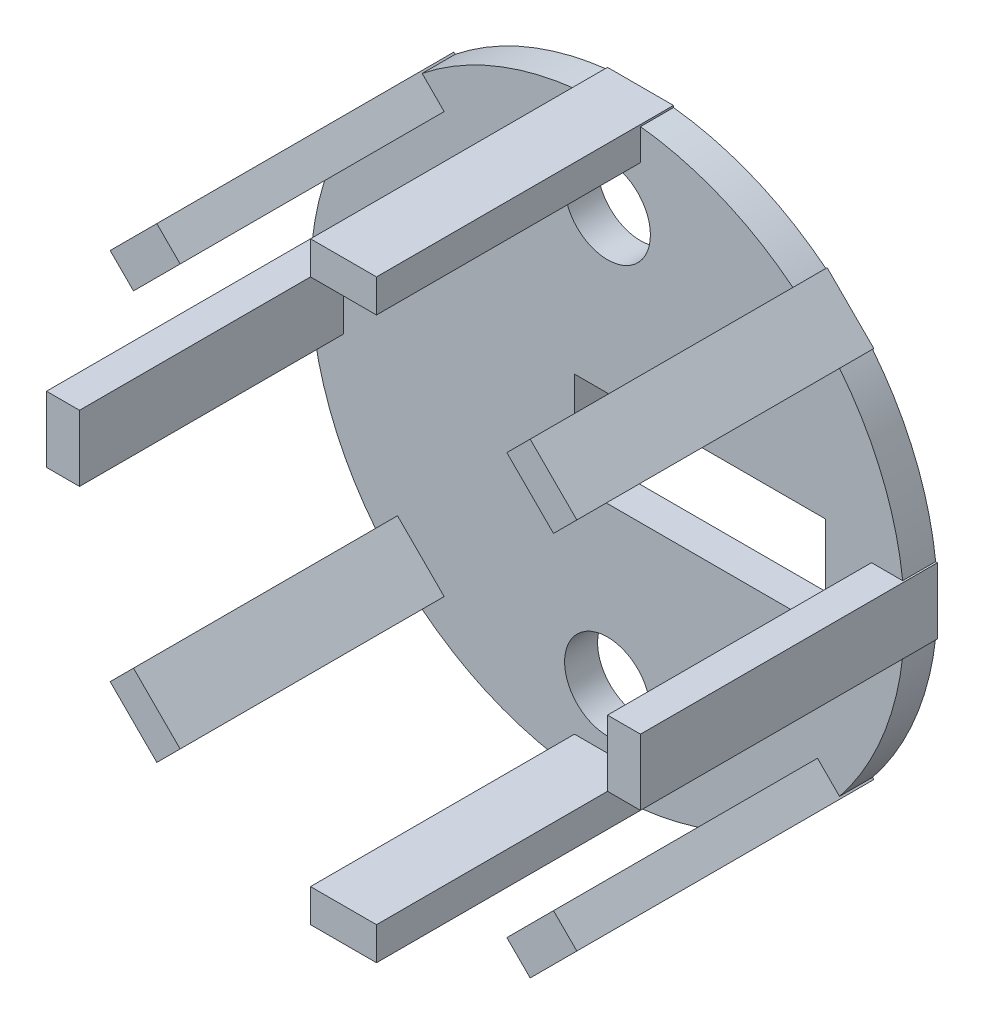
SolidWorks part; units mm, degrees
ref_plane "正面" through (0, 0, 0) normal (0, 0, 1) x (1, 0, 0)
ref_plane "平面" through (0, 0, 0) normal (0, 1, 0) x (1, 0, 0)
ref_plane "右側面" through (0, 0, 0) normal (1, 0, 0) x (0, 0, -1)
sketch "ｽｹｯﾁ1" plane through (0, 0, 0) normal (0, 0, 1) x (1, 0, 0)
  circle A0 centre (0, 0) radius 9
  dimension "D1" = 18
extrude "ﾎﾞｽ - 押し出し1" add sketch "ｽｹｯﾁ1" along normal blind 1
sketch "ｽｹｯﾁ3" plane through (0, 0, 0) normal (0, 0, 1) x (1, 0, 0)
  circle A0 centre (0, 0) radius 10.05
  dimension "D1" = 20.1
extrude "ｶｯﾄ - 押し出し3" [suppressed] cut sketch "ｽｹｯﾁ3" along normal blind 4.5
sketch "ｽｹｯﾁ2" plane through (0, 0, 0) normal (0, 0, 1) x (1, 0, 0)
  circle A0 centre (0, 6.25) radius 1.3
  circle A1 centre (0, -6.25) radius 1.3
  dimension "D1" = 2.6
  dimension "D2" = 2.6
  dimension "D3" = 6.25
  dimension "D4" = 6.25
extrude "ｶｯﾄ - 押し出し1" cut sketch "ｽｹｯﾁ2" along normal through all
sketch "ｽｹｯﾁ4" plane through (0, 0, 0) normal (0, 0, 1) x (1, 0, 0)
  line L5 (6.6, -1.45) -> (0, 0) construction
  line L6 (6.6, 1.45) -> (0, 0) construction
  line L7 (6.6, -1.45) -> (-1, -1.45)
  line L8 (6.6, -1.45) -> (6.6, 1.45)
  line L9 (6.6, 1.45) -> (-1, 1.45)
  line L10 (-1, -1.45) -> (-1, 1.45)
  point P0 (0, 0)
  point P1 (-1, 0)
  dimension "D1" = 2.9
  dimension "D2" = 7.6
  dimension "D3" = 1
extrude "ｶｯﾄ - 押し出し6" cut sketch "ｽｹｯﾁ4" along normal through all
sketch "ｽｹｯﾁ5" plane through (0, 0, 0) normal (0, 0, 1) x (1, 0, 0)
  line L0 (-6.364, 4.9497) -> (-4.9497, 6.364)
  line L1 (-8, -1) -> (-9, -1)
  line L2 (-8, -1) -> (-8, 1)
  line L3 (-8, 1) -> (-9, 1)
  line L4 (-9, -1) -> (-9, 1)
  line L5 (-8, -1) -> (-9, 1) construction
  line L6 (-8, 1) -> (-9, -1) construction
  line L7 (-7.0711, 5.6569) -> (-5.6569, 7.0711)
  line L8 (-4.9497, 6.364) -> (-5.6569, 7.0711)
  line L9 (-6.364, 4.9497) -> (-7.0711, 5.6569)
  line L10 (-1, 8) -> (1, 8)
  line L11 (-1, 9) -> (1, 9)
  line L12 (1, 8) -> (1, 9)
  line L13 (-1, 8) -> (-1, 9)
  line L14 (4.9497, 6.364) -> (6.364, 4.9497)
  line L15 (5.6569, 7.0711) -> (7.0711, 5.6569)
  line L16 (6.364, 4.9497) -> (7.0711, 5.6569)
  line L17 (4.9497, 6.364) -> (5.6569, 7.0711)
  line L18 (8, 1) -> (8, -1)
  line L19 (9, 1) -> (9, -1)
  line L20 (8, -1) -> (9, -1)
  line L21 (8, 1) -> (9, 1)
  line L22 (6.364, -4.9497) -> (4.9497, -6.364)
  line L23 (7.0711, -5.6569) -> (5.6569, -7.0711)
  line L24 (4.9497, -6.364) -> (5.6569, -7.0711)
  line L25 (6.364, -4.9497) -> (7.0711, -5.6569)
  line L26 (1, -8) -> (-1, -8)
  line L27 (1, -9) -> (-1, -9)
  line L28 (-1, -8) -> (-1, -9)
  line L29 (1, -8) -> (1, -9)
  line L30 (-4.9497, -6.364) -> (-6.364, -4.9497)
  line L31 (-5.6569, -7.0711) -> (-7.0711, -5.6569)
  line L32 (-6.364, -4.9497) -> (-7.0711, -5.6569)
  line L33 (-4.9497, -6.364) -> (-5.6569, -7.0711)
  circle A0 centre (0, 0) radius 9 construction
  point P0 (-8.5, 0)
  dimension "D1" = 1
  dimension "D2" = 2
  dimension "D4" = 8.5
  dimension "D3" = 8
extrude "ﾎﾞｽ - 押し出し3" add sketch "ｽｹｯﾁ5" along normal blind 9
sketch "ｽｹｯﾁ6" plane through (0, 0, 0) normal (0, 0, 1) x (1, 0, 0)
  circle A0 centre (-7.9861, -4.15) radius 3
  circle A1 centre (0, 0) radius 9 construction
  circle A2 centre (-9.7943, 3.9253) radius 3
  circle A3 centre (-5.3628, 10.9139) radius 3
  circle A4 centre (2.7125, 12.7221) radius 3
  circle A5 centre (9.7012, 8.2906) radius 3
  circle A6 centre (11.5094, 0.2153) radius 3
  circle A7 centre (7.0779, -6.7733) radius 3
  circle A8 centre (-0.9974, -8.5815) radius 3
  dimension "D2" = 6
  dimension "D3" = 8
  dimension "D1" = 4.15
extrude "ｶｯﾄ - 押し出し7" [suppressed] cut sketch "ｽｹｯﾁ6" along normal blind 5
sketch "ｽｹｯﾁ7" plane through (0, 0, 0) normal (0, 0, 1) x (1, 0, 0)
  circle A0 centre (-8.3179, -3.437) radius 2.5
  circle A1 centre (0, 0) radius 9 construction
  dimension "D1" = 5
extrude "ｶｯﾄ - 押し出し8" [suppressed] cut sketch "ｽｹｯﾁ7" against normal blind 10 and the other way blind 10
pattern_circular "円形ﾊﾟﾀｰﾝ1" [suppressed] count 8 over 360
